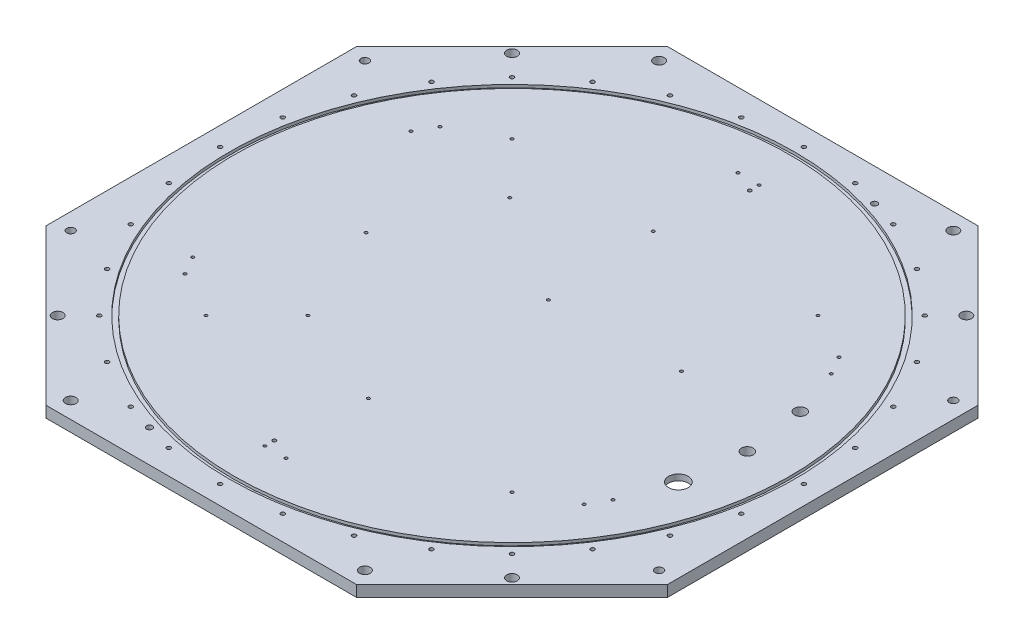
SolidWorks part; units mm, degrees
material "AISI 304"
ref_plane "Front" through (0, 0, 0) normal (0, 0, 1) x (1, 0, 0)
ref_plane "Top" through (0, 0, 0) normal (0, 1, 0) x (1, 0, 0)
ref_plane "Right" through (0, 0, 0) normal (1, 0, 0) x (0, 0, -1)
ref_axis "Axis1" through (0, -5.2388, 0) along (0, 1, 0)
sketch "Sketch1" plane through (0, 0, 0) normal (0, 1, 0) x (1, 0, 0)
  line L0 (-131.9798, 264) -> (131.9798, 264)
  line L1 (131.9798, 264) -> (264, 131.9798)
  line L2 (264, 131.9798) -> (264, -131.9798)
  line L3 (264, 0) -> (0, 0) construction
  line L4 (0, 0) -> (0, 264) construction
  line L5 (131.9798, -264) -> (264, -131.9798)
  line L6 (-131.9798, -264) -> (131.9798, -264)
  line L7 (-131.9798, -264) -> (-264, -131.9798)
  line L8 (-264, 131.9798) -> (-264, -131.9798)
  line L9 (-131.9798, 264) -> (-264, 131.9798)
  point P12 (0, -264)
  point P21 (0, 0)
  dimension "D1" = 528
  dimension "D2" = 280
extrude "Base Plate Profile" add sketch "Sketch1" along normal mid plane 9.525
hole_wizard "M3 Clearance Hole - For Cylinder" positions "Sketch2" profile "Sketch3" hole size "M3" standard "ANSI Metric" end condition up to next
sketch "Sketch2" plane through (0, 4.7625, 0) normal (0, 1, 0) x (1, 0, 0)
  line L0 (-248, 0) -> (248, 0) construction
  point P0 (248, 0)
  point P6 (243.2347, -48.3824)
  point P7 (229.1221, -94.9055)
  point P8 (206.2045, -137.7814)
  point P9 (175.3625, -175.3625)
  point P10 (137.7814, -206.2045)
  point P11 (94.9055, -229.1221)
  point P12 (48.3824, -243.2347)
  point P13 (0, -248)
  point P14 (-48.3824, -243.2347)
  point P15 (-94.9055, -229.1221)
  point P16 (-137.7814, -206.2045)
  point P17 (-175.3625, -175.3625)
  point P18 (-206.2045, -137.7814)
  point P19 (-229.1221, -94.9055)
  point P20 (-243.2347, -48.3824)
  point P21 (-248, 0)
  point P22 (-243.2347, 48.3824)
  point P23 (-229.1221, 94.9055)
  point P24 (-206.2045, 137.7814)
  point P25 (-175.3625, 175.3625)
  point P26 (-137.7814, 206.2045)
  point P27 (-94.9055, 229.1221)
  point P28 (-48.3824, 243.2347)
  point P29 (0, 248)
  point P30 (48.3824, 243.2347)
  point P31 (94.9055, 229.1221)
  point P32 (137.7814, 206.2045)
  point P33 (175.3625, 175.3625)
  point P34 (206.2045, 137.7814)
  point P35 (229.1221, 94.9055)
  point P36 (243.2347, 48.3824)
  dimension "D2" = 496
  dimension "D1" = 32
sketch "Sketch3" plane through (248, 4.7625, 0) normal (1, 0, 0) x (0, 0, 1)
  line L0 (0, 0) -> (0, 9.525)
  line L1 (0, 9.525) -> (1.7, 9.525)
  line L2 (1.7, 9.525) -> (1.7, 0)
  line L5 (1.7, 0) -> (0, 0)
  line L11 (0, -6.35) -> (0, 107.95) construction
  dimension "Thru Hole Dia." = 3.4
  dimension "Thru Hole Depth" = 9.525
hole_wizard "M3x0.5 Tapped Hole - For Support Pillars" positions "Sketch10" profile "Sketch11" tap size "M3x0.5" standard "ANSI Metric"
sketch "Sketch10" plane through (0, 4.7625, 0) normal (0, 1, 0) x (1, 0, 0)
  line L0 (-9, 201) -> (0, 201) construction
  line L1 (0, 201) -> (9, 201) construction
  line L6 (0, 0) -> (0, 201) construction
  line L7 (-9, -201) -> (9, -201) construction
  line L9 (0, -201) -> (0, 0) construction
  point P0 (-9, 201)
  point P2 (9, 201)
  point P39 (169.5711, 108.2942)
  point P40 (178.5711, 92.7058)
  point P41 (178.5711, -92.7058)
  point P42 (169.5711, -108.2942)
  point P43 (9, -201)
  point P44 (-9, -201)
  point P45 (-169.5711, -108.2942)
  point P46 (-178.5711, -92.7058)
  point P47 (-178.5711, 92.7058)
  point P48 (-169.5711, 108.2942)
  dimension "D1" = 18
  dimension "D2" = 6
  dimension "D3" = 201
sketch "Sketch11" plane through (-9, 4.7625, -201) normal (1, 0, 0) x (0, 0, 1)
  line L0 (0, 0) -> (0, 8.2511)
  line L1 (0, 8.2511) -> (1.25, 7.5)
  line L2 (1.25, 7.5) -> (1.25, 0)
  line L5 (1.25, 0) -> (0, 0)
  line L10 (0, 8.2511) -> (-1.25, 7.5) construction
  line L11 (0, -6.35) -> (0, 107.95) construction
  dimension "Tap Drill Dia." = 2.5
  dimension "Tap Drill Depth" = 7.5
  dimension "Drill Angle" = 118
cosmetic thread "Hole Thread1" parameters "D1"=6, "D2"=3
cosmetic thread "Hole Thread2" parameters "D1"=6, "D2"=3
cosmetic thread "Hole Thread3" parameters "D1"=6, "D2"=3
cosmetic thread "Hole Thread4" parameters "D1"=6, "D2"=3
cosmetic thread "Hole Thread5" parameters "D1"=6, "D2"=3
cosmetic thread "Hole Thread6" parameters "D1"=6, "D2"=3
cosmetic thread "Hole Thread7" parameters "D1"=6, "D2"=3
cosmetic thread "Hole Thread8" parameters "D1"=6, "D2"=3
cosmetic thread "Hole Thread9" parameters "D1"=6, "D2"=3
cosmetic thread "Hole Thread10" parameters "D1"=6, "D2"=3
cosmetic thread "Hole Thread11" parameters "D1"=6, "D2"=3
cosmetic thread "Hole Thread12" parameters "D1"=6, "D2"=3
hole_wizard "Ø3.0mm Dowel Hole - For Support Pillars" positions "Sketch12" profile "Sketch13" hole size "Ø3.0" standard "ANSI Metric"
sketch "Sketch12" plane through (0, 4.7625, 0) normal (0, 1, 0) x (1, 0, 0)
  line L1 (9, 193) -> (9, 201) construction
  line L3 (-9, -201) -> (-9, -193) construction
  point P0 (9, 193)
  point P2 (-9, -193)
  dimension "D1" = 8
sketch "Sketch13" plane through (9, 4.7625, -193) normal (1, 0, 0) x (0, 0, 1)
  line L0 (0, 0) -> (0, 6.9013)
  line L1 (0, 6.9013) -> (1.5, 6)
  line L2 (1.5, 6) -> (1.5, 0)
  line L5 (1.5, 0) -> (0, 0)
  line L10 (0, 6.9013) -> (-1.5, 6) construction
  line L11 (0, -6.35) -> (0, 107.95) construction
  dimension "Hole Dia." = 3
  dimension "Hole Depth" = 6
  dimension "Drill Angle" = 118
hole_wizard "M3x0.5 Tapped Hole - For PCB Standoffs" positions "Sketch14" profile "Sketch15" tap size "M3x0.5" standard "ANSI Metric"
sketch "Sketch14" plane through (0, 4.7625, 0) normal (0, 1, 0) x (1, 0, 0)
  line L13 (-150, -150) -> (150, -150) construction
  line L14 (-150, -150) -> (-150, 150) construction
  line L15 (-150, 150) -> (150, 150) construction
  line L16 (150, -150) -> (150, 150) construction
  line L17 (-150, -150) -> (150, 150) construction
  line L18 (-150, 150) -> (150, -150) construction
  point P133 (-130, -130)
  point P136 (130, -130)
  point P138 (130, 130)
  point P140 (-130, 130)
  point P143 (-86.8, -86.7)
  point P145 (0, -122)
  point P149 (-123, -1)
  point P152 (-87.7, 85.8)
  point P154 (4, 27)
  point P157 (-2, 122)
  point P159 (113, 31)
  dimension "D1" = 300
  dimension "D3" = 63.2
  dimension "D4" = 63.3
  dimension "D5" = 28
  dimension "D2" = 20
  dimension "D6" = 27
  dimension "D7" = 149
  dimension "D8" = 235.8
  dimension "D9" = 62.3
  dimension "D10" = 154
  dimension "D11" = 177
  dimension "D12" = 148
  dimension "D13" = 272
  dimension "D14" = 181
  dimension "D15" = 263
sketch "Sketch15" plane through (113, 4.7625, -31) normal (1, 0, 0) x (0, 0, 1)
  line L0 (0, 0) -> (0, 7.2511)
  line L1 (0, 7.2511) -> (1.25, 6.5)
  line L2 (1.25, 6.5) -> (1.25, 0)
  line L5 (1.25, 0) -> (0, 0)
  line L10 (0, 7.2511) -> (-1.25, 6.5) construction
  line L11 (0, -6.35) -> (0, 107.95) construction
  dimension "Tap Drill Dia." = 2.5
  dimension "Tap Drill Depth" = 6.5
  dimension "Drill Angle" = 118
cosmetic thread "Hole Thread13" parameters "D1"=5, "D2"=3
cosmetic thread "Hole Thread14" parameters "D1"=5, "D2"=3
cosmetic thread "Hole Thread15" parameters "D1"=5, "D2"=3
cosmetic thread "Hole Thread16" parameters "D1"=5, "D2"=3
cosmetic thread "Hole Thread17" parameters "D1"=5, "D2"=3
cosmetic thread "Hole Thread18" parameters "D1"=5, "D2"=3
cosmetic thread "Hole Thread19" parameters "D1"=5, "D2"=3
cosmetic thread "Hole Thread20" parameters "D1"=5, "D2"=3
cosmetic thread "Hole Thread21" parameters "D1"=5, "D2"=3
cosmetic thread "Hole Thread22" parameters "D1"=5, "D2"=3
cosmetic thread "Hole Thread23" parameters "D1"=5, "D2"=3
sketch "PCB Size Outline" plane through (0, -4.7625, 0) normal (0, -1, 0) x (1, 0, 0)
  line L1 (-150, -150) -> (150, -150)
  line L2 (-150, -150) -> (-150, 150)
  line L3 (-150, 150) -> (150, 150)
  line L4 (150, -150) -> (150, 150)
  line L5 (-150, -150) -> (150, 150) construction
  line L6 (-150, 150) -> (150, -150) construction
  point P0 (0, 0)
  dimension "D1" = 300
hole_wizard "M8 Clearance Hole - For Lifting / Alignment" positions "Sketch16" profile "Sketch17" hole size "M8" standard "ANSI Metric" end condition up to next
sketch "Sketch16" plane through (0, 4.7625, 0) normal (0, 1, 0) x (1, 0, 0)
  line L0 (-193.0402, 193.0402) -> (-193.0402, -193.0402) construction
  line L1 (-193.0402, -193.0402) -> (193.0402, -193.0402) construction
  line L2 (193.0402, -193.0402) -> (193.0402, 193.0402) construction
  line L3 (193.0402, 193.0402) -> (-193.0402, 193.0402) construction
  line L5 (-193.0402, 193.0402) -> (193.0402, -193.0402) construction
  point P0 (-193.0402, -193.0402)
  point P6 (-193.0402, 193.0402)
  point P7 (193.0402, 193.0402)
  point P8 (193.0402, -193.0402)
  dimension "D2" = 546
  dimension "D1" = 4
sketch "Sketch17" plane through (-193.0402, 4.7625, 193.0402) normal (1, 0, 0) x (0, 0, 1)
  line L0 (0, 0) -> (0, 9.525)
  line L1 (0, 9.525) -> (4.5, 9.525)
  line L2 (4.5, 9.525) -> (4.5, 0)
  line L5 (4.5, 0) -> (0, 0)
  line L11 (0, -6.35) -> (0, 107.95) construction
  dimension "Thru Hole Dia." = 9
  dimension "Thru Hole Depth" = 9.525
hole_wizard "M8x1.25 Tapped Hole -For Super Structure" positions "Sketch18" profile "Sketch19" tap size "M8x1.25" standard "ANSI Metric" end condition up to next
sketch "Sketch18" plane through (0, 4.7625, 0) normal (0, 1, 0) x (1, 0, 0)
  line L0 (-264, 0) -> (0, 0) construction
  line L1 (-264, 131.9798) -> (-264, -131.9798) construction
  line L2 (0, 0) -> (0, -264) construction
  line L3 (-131.9798, -264) -> (131.9798, -264) construction
  line L5 (0, 0) -> (-197.9899, -197.9899) construction
  line L6 (-264, -131.9798) -> (-131.9798, -264) construction
  point P22 (-250, -125)
  point P25 (-250, 125)
  point P27 (250, -125)
  point P28 (250, 125)
  dimension "D2" = 250
  dimension "D3" = 500
sketch "Sketch19" plane through (250, 4.7625, -125) normal (1, 0, 0) x (0, 0, 1)
  line L0 (0, 0) -> (0, 9.525)
  line L1 (0, 9.525) -> (3.4, 9.525)
  line L2 (3.4, 9.525) -> (3.4, 0)
  line L5 (3.4, 0) -> (0, 0)
  line L11 (0, -6.35) -> (0, 107.95) construction
  dimension "Thru Tap Drill Dia." = 6.8
  dimension "Thru Tap Drill Depth" = 9.525
cosmetic thread "Hole Thread34" parameters "D2"=8
cosmetic thread "Hole Thread35" parameters "D2"=8
cosmetic thread "Hole Thread37" parameters "D2"=8
cosmetic thread "Hole Thread39" parameters "D2"=8
hole_wizard "7/16-20 Tapped Hole - For Penetrator" positions "Sketch25" profile "Sketch26" tap size "7/16-20" standard "ANSI Inch" end condition up to next
sketch "Sketch25" plane through (0, -4.7625, 0) normal (0, -1, 0) x (-1, 0, 0)
  point P0 (-200, 0)
  dimension "D1" = 200
cosmetic thread "Hole Thread32" parameters "D2"=11.1125
sketch "Sketch26" plane through (200, -4.7625, 0) normal (1, 0, 0) x (0, 0, -1)
  line L0 (0, 0) -> (0, 9.525)
  line L1 (0, 9.525) -> (4.9606, 9.525)
  line L2 (4.9606, 9.525) -> (4.9606, 0)
  line L5 (4.9606, 0) -> (0, 0)
  line L11 (0, -6.35) -> (0, 107.95) construction
  dimension "Thru Tap Drill Dia." = 9.9212
  dimension "Thru Tap Drill Depth" = 9.525
sketch "Sketch28" plane through (0, 4.7625, 0) normal (0, 1, 0) x (1, 0, 0)
  line L0 (-150, -150) -> (150, 150) construction
  circle A0 centre (0, 0) radius 240.5
  circle A1 centre (0, 0) radius 236.3344
  dimension "D1" = 481
  dimension "D2" = 4.1656
extrude "O-ring Groove" cut sketch "Sketch28" against normal blind 2.413
sketch "Sketch_thickness" [suppressed] plane through (0, 0, 0) normal (1, 0, 0) x (0, 0, -1)
  line L0 (-88.2215, 4.7625) -> (-88.2215, -0.2425)
  line L1 (-131.9798, 4.7625) -> (131.9798, 4.7625) construction
  line L2 (-88.2215, -0.2425) -> (-88.2215, -4.7625)
  line L3 (-150, -4.7625) -> (150, -4.7625) construction
  dimension "D1" = 5.005
  dimension "D2" = 4.52
pattern_circular "CirPattern_extraCables" count 2 every 15 about axis through (0, -5.2388, 0) along (0, 1, 0) of "7/16-20 Tapped Hole - For Penetrator"
hole_wizard "5/8 Clearance Hole1" positions "Sketch32" profile "Sketch33" hole size "5/8" standard "ANSI Inch" end condition up to next
sketch "Sketch32" plane through (0, 4.7625, 0) normal (0, 1, 0) x (1, 0, 0)
  line L0 (0, 0) -> (193.1852, -51.7638) construction
  line L2 (0, 0) -> (200, 0) construction
  point P0 (193.1852, -51.7638)
  dimension "D1" = 200
  dimension "D2" = 15
sketch "Sketch33" plane through (193.1852, 4.7625, 51.7638) normal (1, 0, 0) x (0, 0, 1)
  line L0 (0, 0) -> (0, 9.525)
  line L1 (0, 9.525) -> (8.3337, 9.525)
  line L2 (8.3337, 9.525) -> (8.3337, 0)
  line L5 (8.3337, 0) -> (0, 0)
  line L11 (0, -6.35) -> (0, 107.95) construction
  dimension "Thru Hole Dia." = 16.6675
  dimension "Thru Hole Depth" = 9.525
sketch "Sketch35" plane through (0, -4.7625, 0) normal (0, -1, 0) x (1, 0, 0)
  circle A0 centre (193.1852, 51.7638) radius 18
  dimension "D1" = 36
extrude "Cut-Extrude1" cut sketch "Sketch35" against normal blind 4.5
hole_wizard "M8 Clearance Hole" positions "Sketch37" profile "Sketch39" hole size "M8" standard "ANSI Metric" end condition up to next
sketch "Sketch37" plane through (-28.1239, 4.7625, -48.0675) normal (0, 1, 0) x (1, 0, 0)
  line L0 (-235.8761, -48.0675) -> (28.1239, -48.0675) construction
  line L2 (28.1239, -48.0675) -> (28.1239, -312.0675) construction
  line L5 (28.1239, -48.0675) -> (-169.866, -246.0574) construction
  line L7 (-103.8559, -312.0675) -> (160.1037, -312.0675) construction
  line L8 (-235.8761, 83.9123) -> (-235.8761, -180.0473) construction
  line L9 (-235.8761, -180.0473) -> (-103.8559, -312.0675) construction
  point P0 (-96.8761, -298.0675)
  point P24 (-96.8761, 201.9325)
  point P26 (153.1239, -298.0675)
  point P29 (153.1239, 201.9325)
  dimension "D1" = 250
  dimension "D2" = 500
sketch "Sketch39" plane through (-125, 4.7625, 250) normal (1, 0, 0) x (0, 0, 1)
  line L0 (0, 0) -> (0, 9.525)
  line L1 (0, 9.525) -> (4.5, 9.525)
  line L2 (4.5, 9.525) -> (4.5, 0)
  line L5 (4.5, 0) -> (0, 0)
  line L11 (0, -6.35) -> (0, 107.95) construction
  dimension "Thru Hole Dia." = 9
  dimension "Thru Hole Depth" = 9.525
hole_wizard "Ø5.0mm Dowel Hole1" positions "Sketch42" profile "Sketch43" hole size "Ø5.0" standard "ANSI Metric"
sketch "Sketch42" plane through (0, 4.7625, 0) normal (0, 1, 0) x (1, 0, 0)
  point P0 (71.7003, 236.3643)
  point P3 (-71.7003, -236.3643)
sketch "Sketch43" plane through (71.7003, 4.7625, -236.3643) normal (1, 0, 0) x (0, 0, 1)
  line L0 (0, 0) -> (0, 6.5172)
  line L1 (0, 6.5172) -> (2.525, 5)
  line L2 (2.525, 5) -> (2.525, 0)
  line L5 (2.525, 0) -> (0, 0)
  line L10 (0, 6.5172) -> (-2.525, 5) construction
  line L11 (0, -6.35) -> (0, 107.95) construction
  dimension "Hole Dia." = 5.05
  dimension "Hole Depth" = 5
  dimension "Drill Angle" = 118
